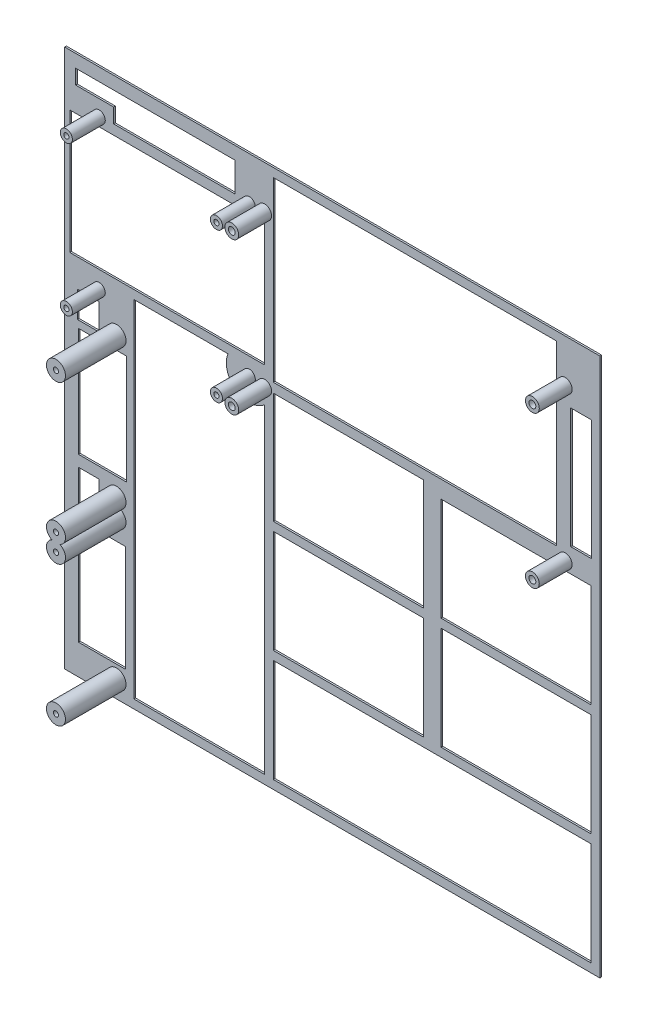
SolidWorks part; units mm, degrees
ref_plane "Front Plane" through (0, 0, 0) normal (0, 0, 1) x (1, 0, 0)
ref_plane "Top Plane" through (0, 0, 0) normal (0, 1, 0) x (1, 0, 0)
ref_plane "Right Plane" through (0, 0, 0) normal (1, 0, 0) x (0, 0, -1)
sketch "Sketch2" plane through (0, 0, 0) normal (0, 0, 1) x (1, 0, 0)
  line L1 (-20, 111.36) -> (289.367, 111.36)
  line L2 (-20, 111.36) -> (-20, -200)
  line L3 (-20, -200) -> (289.367, -200)
  line L4 (289.367, 111.36) -> (289.367, -200)
  circle A0 centre (0, 86.36) radius 1.5
  circle A1 centre (86.741, 86.36) radius 1.5
  circle A2 centre (0, 0) radius 1.5
  circle A3 centre (86.741, 0) radius 1.5
  circle A4 centre (95.631, -1.16) radius 2
  circle A5 centre (95.631, 86.61) radius 2
  circle A6 centre (269.367, 86.61) radius 2
  circle A7 centre (269.367, -1.16) radius 2
  dimension "D1" = 3
  dimension "D8" = 4
  dimension "D2" = 86.741
  dimension "D3" = 86.36
  dimension "D4" = 173.736
  dimension "D5" = 8.89
  dimension "D6" = 0.25
  dimension "D7" = 1.16
  dimension "D9" = 20
  dimension "D10" = 200
  dimension "D11" = 25
  dimension "D12" = 20
extrude "Boss-Extrude1" add sketch "Sketch2" along normal blind 1 contours L2 L3 L4 L1
extrude "Extrude-Thin1" add sketch "Sketch2<3>" along normal blind 20 thin contours A2 | A3 | A4 | A1 | A0 | A5 | A6 | A7 thin type one direction wall 2
sketch "Sketch2<3>" plane through (0, 0, 0) normal (0, 0, 1) x (1, 0, 0) same geometry as "Sketch2"
sketch "Sketch3" plane through (0, 0, 1) normal (0, 0, 1) x (1, 0, 0)
  line L0 (-20, 111.36) -> (-20, -200) construction
  line L1 (-20, -200) -> (289.367, -200) construction
  circle A0 centre (10, -18) radius 1.5
  circle A1 centre (10, -99) radius 1.5
  circle A2 centre (10, -109) radius 1.5
  circle A3 centre (10, -190) radius 1.5
  dimension "D1" = 3
  dimension "D2" = 81
  dimension "D3" = 81
  dimension "D4" = 10
  dimension "D5" = 30
  dimension "D6" = 10
extrude "Extrude-Thin2" add sketch "Sketch3" along normal blind 35 thin thin type one direction wall 4
sketch "Sketch4" plane through (0, 0, 1) normal (0, 0, 1) x (1, 0, 0)
  line L1 (-17, 81.36) -> (95.631, 81.36)
  line L2 (-17, 81.36) -> (-17, 10)
  line L3 (-17, 10) -> (95.631, 10)
  line L4 (95.631, 81.36) -> (95.631, 10)
  line L5 (100.631, 106.36) -> (264.367, 106.36)
  line L6 (100.631, 106.36) -> (100.631, 3.84)
  line L7 (100.631, 3.84) -> (264.367, 3.84)
  line L8 (264.367, 106.36) -> (264.367, 3.84)
  line L9 (100.631, -1.5906) -> (187.499, -1.5906)
  line L10 (100.631, -1.5906) -> (100.631, -65.7733)
  line L11 (100.631, -65.7733) -> (187.499, -65.7733)
  line L12 (187.499, -1.5906) -> (187.499, -65.7733)
  line L13 (284.367, -6.16) -> (197.499, -6.16)
  line L14 (284.367, -6.16) -> (284.367, -65.7733)
  line L15 (284.367, -65.7733) -> (197.499, -65.7733)
  line L16 (197.499, -6.16) -> (197.499, -65.7733)
  line L17 (100.631, -70.7733) -> (187.499, -70.7733)
  line L18 (100.631, -70.7733) -> (100.631, -130.3867)
  line L19 (100.631, -130.3867) -> (187.499, -130.3867)
  line L20 (187.499, -70.7733) -> (187.499, -130.3867)
  line L21 (197.499, -70.7733) -> (284.367, -70.7733)
  line L22 (197.499, -70.7733) -> (197.499, -130.3867)
  line L23 (197.499, -130.3867) -> (284.367, -130.3867)
  line L24 (284.367, -70.7733) -> (284.367, -130.3867)
  line L25 (20, 5) -> (74.4407, 5)
  line L26 (20, 5) -> (20, -195)
  line L27 (20, -195) -> (95.631, -195)
  line L28 (95.631, -9.8623) -> (95.631, -195)
  line L29 (100.631, -135.3867) -> (284.367, -135.3867)
  line L30 (100.631, -135.3867) -> (100.631, -195)
  line L31 (100.631, -195) -> (284.367, -195)
  line L32 (284.367, -135.3867) -> (284.367, -195)
  line L33 (8.3041, 103.9512) -> (78.3688, 103.9512)
  line L34 (8.3041, 95.4874) -> (8.3041, 87.0236)
  line L35 (8.3041, 87.0236) -> (78.3688, 87.0236)
  line L36 (-20, -200) -> (289.367, -200) construction
  line L37 (289.367, 111.36) -> (289.367, -200) construction
  line L38 (-20, 111.36) -> (289.367, 111.36) construction
  line L39 (-22, 113.36) -> (-22, -202) construction
  line L40 (78.3688, 103.9512) -> (78.3688, 87.0236)
  line L41 (-13.6448, 103.9512) -> (8.3041, 103.9512)
  line L42 (-13.6448, 103.9512) -> (-13.6448, 95.4874)
  line L43 (-13.6448, 95.4874) -> (8.3041, 95.4874)
  line L45 (272.5384, 76.9674) -> (284.6174, 76.9674)
  line L46 (272.5384, 76.9674) -> (272.5384, 7.5055)
  line L47 (272.5384, 7.5055) -> (284.6174, 7.5055)
  line L48 (284.6174, 76.9674) -> (284.6174, 7.5055)
  line L49 (-12, -121.0945) -> (15.2215, -121.0945)
  line L50 (-12, -121.0945) -> (-12, -182.5702)
  line L51 (-12, -182.5702) -> (15.2215, -182.5702)
  line L52 (15.2215, -121.0945) -> (15.2215, -182.5702)
  line L53 (-12, -25.4711) -> (15.8287, -25.4711)
  line L54 (-12, -25.4711) -> (-12, -88.5337)
  line L55 (-12, -88.5337) -> (15.8287, -88.5337)
  line L56 (15.8287, -25.4711) -> (15.8287, -88.5337)
  line L57 (-12, -95) -> (0, -95)
  line L58 (-12, -95) -> (-12, -113.5023)
  line L59 (-12, -113.5023) -> (0, -113.5023)
  line L60 (0, -95) -> (0, -113.5023)
  line L65 (-12.5782, -6.16) -> (0, -6.16)
  line L66 (-12.5782, -6.16) -> (-12.5782, -21.3398)
  line L67 (-12.5782, -21.3398) -> (0, -21.3398)
  line L68 (0, -6.16) -> (0, -21.3398)
  arc A0 (74.4407, 5) -> (95.631, -9.8623) centre (86.741, 0) ccw
  circle A2 centre (10, -18) radius 1.5 construction
  circle A3 centre (269.367, -1.16) radius 2 construction
  circle A4 centre (269.367, 86.61) radius 2 construction
  circle A5 centre (95.631, 86.61) radius 2 construction
  circle A6 centre (86.741, 86.36) radius 1.5 construction
  dimension "D14" = 5
  dimension "D1" = 5
  dimension "D2" = 5
  dimension "D3" = 5
  dimension "D4" = 5
  dimension "D5" = 10
  dimension "D6" = 5
  dimension "D7" = 5
  dimension "D8" = 5
  dimension "D9" = 5
  dimension "D10" = 5
  dimension "D11" = 5
  dimension "D12" = 10
  dimension "D15" = 5
  dimension "D16" = 10
  dimension "D17" = 5
  dimension "D18" = 5
  dimension "D19" = 5
  dimension "D20" = 10
extrude "Cut-Extrude1" cut sketch "Sketch4" against normal through all
